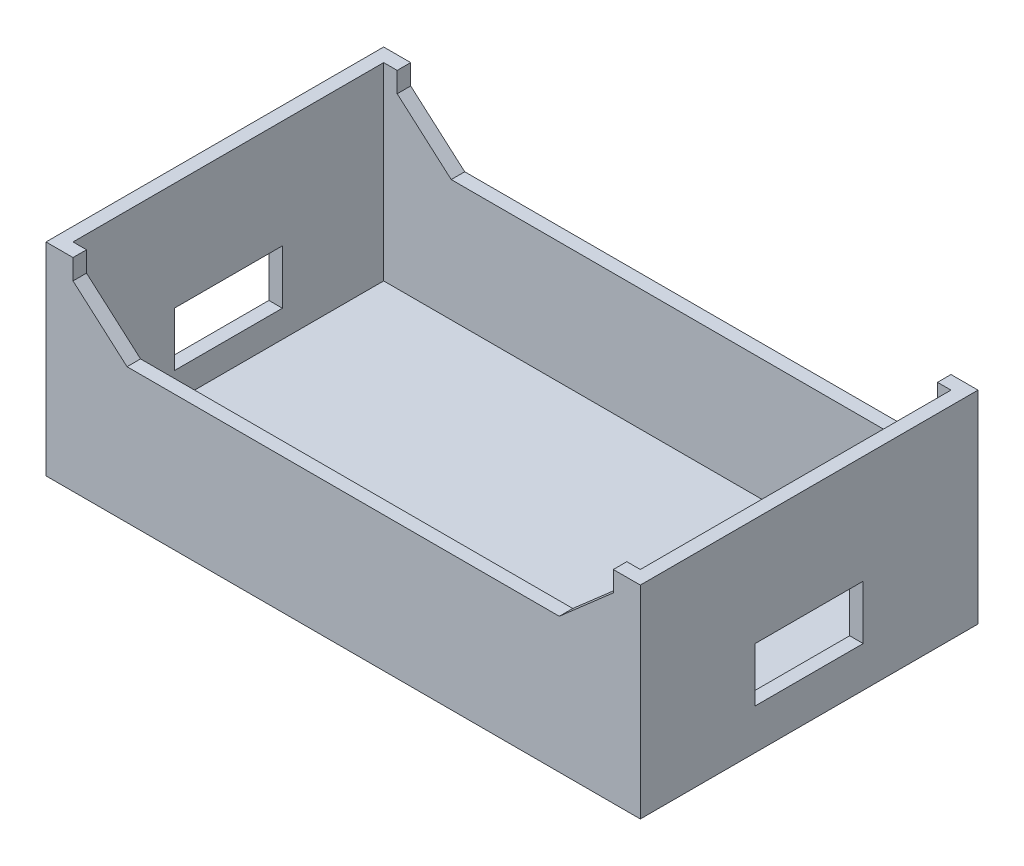
SolidWorks part; units mm, degrees
material "ABS"
ref_plane "Alzado" through (0, 0, 0) normal (0, 0, 1) x (1, 0, 0)
ref_plane "Planta" through (0, 0, 0) normal (0, 1, 0) x (1, 0, 0)
ref_plane "Vista lateral" through (0, 0, 0) normal (1, 0, 0) x (0, 0, -1)
sketch "Croquis1" plane through (0, 0, 0) normal (0, 1, 0) x (1, 0, 0)
  line L1 (22, -12.5) -> (-22, -12.5)
  line L2 (22, -12.5) -> (22, 12.5)
  line L3 (22, 12.5) -> (-22, 12.5)
  line L4 (-22, -12.5) -> (-22, 12.5)
  line L5 (22, -12.5) -> (-22, 12.5) construction
  line L6 (22, 12.5) -> (-22, -12.5) construction
  point P0 (0, 0)
  dimension "D1" = 25
  dimension "D2" = 44
extrude "Saliente-Extruir2" add sketch "Croquis1" along normal blind 10
sketch "Croquis2" plane through (0, 10, 0) normal (0, 1, 0) x (1, 0, 0)
  line L0 (22, 12.5) -> (-22, 12.5) construction
  line L1 (21, -11.5) -> (-21, -11.5)
  line L2 (21, -11.5) -> (21, 11.5)
  line L3 (21, 11.5) -> (-21, 11.5)
  line L4 (-21, -11.5) -> (-21, 11.5)
  line L5 (21, -11.5) -> (-21, 11.5) construction
  line L6 (21, 11.5) -> (-21, -11.5) construction
  line L7 (-22, 12.5) -> (-22, -12.5) construction
  point P0 (0, 0)
  dimension "D1" = 1
  dimension "D2" = 1
extrude "Cortar-Extruir1" cut sketch "Croquis2" against normal blind 9
sketch "Croquis3" plane through (0, 0, 12.5) normal (0, 0, 1) x (1, 0, 0)
  line L0 (0, 10) -> (0, 15.8262)
  line L1 (-22, 10) -> (22, 10) construction
  line L2 (-22, 10) -> (-23, 10)
  line L3 (-22, 10) -> (-22, 0) construction
  line L4 (-23, 10) -> (-23, 15)
  line L5 (-23, 15) -> (-20, 15)
  line L6 (-20, 15) -> (-20, 13.5)
  line L7 (-23, 10) -> (-16, 10)
  line L8 (-16, 10) -> (-20, 13.5)
  line L9 (16, 10) -> (20, 13.5)
  line L10 (23, 10) -> (16, 10)
  line L11 (20, 15) -> (20, 13.5)
  line L12 (23, 10) -> (23, 15)
  line L13 (22, 10) -> (23, 10)
  line L14 (-23, 10) -> (-23, 8)
  line L15 (-23, 8) -> (-22, 8)
  line L16 (-22, 8) -> (-22, 10)
  line L17 (22, 8) -> (22, 10)
  line L18 (23, 8) -> (22, 8)
  line L19 (23, 10) -> (23, 8)
  line L20 (22, 10) -> (23, 10)
  line L21 (20, 15) -> (23, 15)
  line M2 (22, 0) -> (22, 10)
  line M3 (22, 10) -> (-22, 10)
  line M4 (-22, 10) -> (-22, 0)
extrude "Saliente-Extruir3" add sketch "Croquis3" against normal blind 25 contours L8 L6 L5 L4 L2 M3 | L21 L11 L9 L10 L12 M3 | L14 L15 L2 M4 | L19 L10 L18 M2 region at (-22.5, 9, 12.5) region at (-20.5985, 12.0758, 12.5) region at (20.5985, 12.0758, 12.5) region at (22.5, 9, 12.5)
sketch "Croquis4" plane through (0, 1, 0) normal (0, 1, 0) x (1, 0, 0)
  line L0 (21, 11.5) -> (-21, 11.5) construction
  line L1 (21, -11.5) -> (-21, -11.5)
  line L2 (21, -11.5) -> (21, 11.5)
  line L3 (21, 11.5) -> (-21, 11.5)
  line L4 (-21, -11.5) -> (-21, 11.5)
  line L5 (21, -11.5) -> (-21, 11.5) construction
  line L6 (21, 11.5) -> (-21, -11.5) construction
  point P0 (0, 0)
extrude "Cortar-Extruir2" cut sketch "Croquis4" along normal blind 28
sketch "Croquis5" plane through (0, 15, 0) normal (0, 1, 0) x (1, 0, 0)
  line L0 (-23, 12.5) -> (-21, -12.5)
  line L1 (-23, -12.5) -> (-20, -12.5) construction
  line L2 (-23, 12.5) -> (-22, 12.5)
  line L3 (-22, 12.5) -> (-21, 12.5)
  line L4 (-23, 12.5) -> (-20, 12.5) construction
  line L5 (0, 0) -> (0, -16.8215)
  line L6 (-22, 12.5) -> (-21, 12.5)
  line L7 (-22, 12.5) -> (-22, -12.5)
  line L8 (-22, -12.5) -> (-21, -12.5)
  line L9 (-21, 12.5) -> (-21, -12.5)
  line L10 (21, 12.5) -> (21, -12.5)
  line L11 (22, -12.5) -> (21, -12.5)
  line L12 (22, 12.5) -> (22, -12.5)
  line L13 (22, 12.5) -> (21, 12.5)
  line L14 (22, 12.5) -> (21, 12.5)
  line L15 (23, 12.5) -> (22, 12.5)
  line L16 (23, 12.5) -> (21, -12.5)
  line L17 (21, -11.5) -> (22, -11.5)
  line L19 (21, 11.5) -> (22, 11.5)
  line L20 (21, 11.5) -> (21, -11.5)
  line L21 (21, -11.5) -> (22, -11.5)
  line L22 (22, 11.5) -> (22, -11.5)
  line L23 (-21, 11.5) -> (-22, 11.5)
  line L24 (-21, 11.5) -> (-21, -11.5)
  line L25 (-21, -11.5) -> (-22, -11.5)
  line L26 (-22, 11.5) -> (-22, -11.5)
extrude "Cortar-Extruir10" cut sketch "Croquis5" against normal blind 5 contours L25 L5 L23 L7 L0 | L25 L0 L7 | L19 L10 L17 L16 L12 | L16 L17 L12 region at (-21.4423, 15, -2.29) region at (-21.6933, 15, 7.6667) region at (21.4423, 15, -2.29) region at (21.6933, 15, 7.6667)
sketch "Croquis6" plane through (23, 0, 0) normal (1, 0, 0) x (0, 0, -1)
  line L1 (-15.4714, 16.8377) -> (14.422, 16.8377)
  line L2 (-15.4714, 16.8377) -> (-15.4714, 5.3904)
  line L3 (-15.4714, 5.3904) -> (14.422, 5.3904)
  line L4 (14.422, 16.8377) -> (14.422, 5.3904)
extrude "Cortar-Extruir11" cut sketch "Croquis6" against normal blind 1
sketch "Croquis7" plane through (-23, 0, 0) normal (-1, 0, 0) x (0, 0, 1)
  line L1 (-16.2316, 17.1898) -> (14.7722, 17.1898)
  line L2 (-16.2316, 17.1898) -> (-16.2316, 7.3211)
  line L3 (-16.2316, 7.3211) -> (14.7722, 7.3211)
  line L4 (14.7722, 17.1898) -> (14.7722, 7.3211)
extrude "Cortar-Extruir12" cut sketch "Croquis7" against normal blind 1
sketch "Croquis8" plane through (0, 10, 0) normal (0, 1, 0) x (1, 0, 0)
  line L0 (0, 0) -> (0, 8.9095)
  line L1 (-21, -11.5) -> (-22, -11.5)
  line L2 (-21, -11.5) -> (-21, 11.5)
  line L3 (-21, 11.5) -> (-22, 11.5)
  line L4 (-22, -11.5) -> (-22, 11.5)
  line L5 (22, -11.5) -> (22, 11.5)
  line L6 (21, 11.5) -> (22, 11.5)
  line L7 (21, -11.5) -> (21, 11.5)
  line L8 (21, -11.5) -> (22, -11.5)
  line M1 (-22, -11.5) -> (-21, -11.5)
  line M2 (-21, -11.5) -> (-21, 11.5)
  line M3 (-21, 11.5) -> (-22, 11.5)
  line M4 (-22, 11.5) -> (-22, -11.5)
extrude "Saliente-Extruir4" add sketch "Croquis8" along normal blind 5 contours M4 M1 M2 M3 | L7 L8 L5 L6 region at (-21.5, 10, 0) region at (21.5, 10, 0)
sketch "Croquis9" plane through (-22, 0, 0) normal (-1, 0, 0) x (0, 0, 1)
  line L0 (12.5, 15) -> (-12.5, 15) construction
  line L1 (-4, 7) -> (4, 7)
  line L2 (-4, 7) -> (-4, 3)
  line L3 (-4, 3) -> (4, 3)
  line L4 (4, 7) -> (4, 3)
  line L5 (-4, 7) -> (4, 3) construction
  line L6 (-4, 3) -> (4, 7) construction
  line L7 (-12.5, 0) -> (12.5, 0) construction
  line L8 (-12.5, 15) -> (-12.5, 0) construction
  point P0 (0, 5)
  dimension "D1" = 8
  dimension "D2" = 4
  dimension "D3" = 8
  dimension "D4" = 8.5
extrude "Cortar-Extruir17" cut sketch "Croquis9" against normal blind 87
